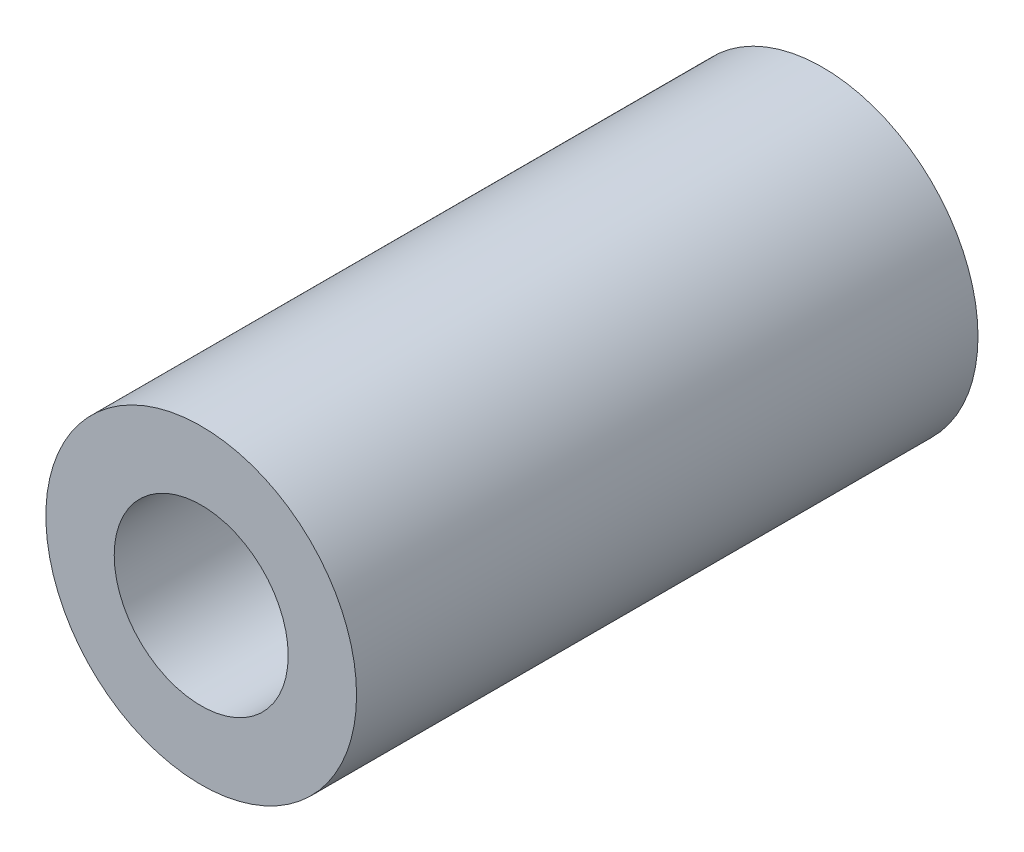
SolidWorks part; units mm, degrees
ref_plane "Front Plane" through (0, 0, 0) normal (0, 0, 1) x (1, 0, 0)
ref_plane "Top Plane" through (0, 0, 0) normal (0, 1, 0) x (1, 0, 0)
ref_plane "Right Plane" through (0, 0, 0) normal (1, 0, 0) x (0, 0, -1)
sketch "Sketch1" plane through (0, 0, 0) normal (0, 0, 1) x (1, 0, 0)
  circle A0 centre (0, 0) radius 3.175
  circle A1 centre (0, 0) radius 1.778
  dimension "OD" = 6.35
  dimension "ID" = 3.556
extrude "Extrude1" add sketch "Sketch1" along normal mid plane 12.7
sketch "Sketch2" plane through (0, 0, 0) normal (1, 0, 0) x (0, 0, -1)
  line L0 (-6.35, -1.778) -> (6.35, -1.778) construction
  line L3 (6.35, 1.778) -> (-6.35, 1.778) construction
  line L5 (-6.35, -1.778) -> (6.35, -1.778)
  line L6 (6.35, 1.778) -> (-6.35, 1.778)
sketch "Sketch4" plane through (0, 0, 6.35) normal (0, 0, 1) x (1, 0, 0)
  line L0 (0, 0) -> (-1.2572, 1.2572)
  line L1 (0, -2.1828) -> (0, 2.1828) construction
  circle A0 centre (0, 0) radius 1.778 construction
  dimension "D1" = 45
